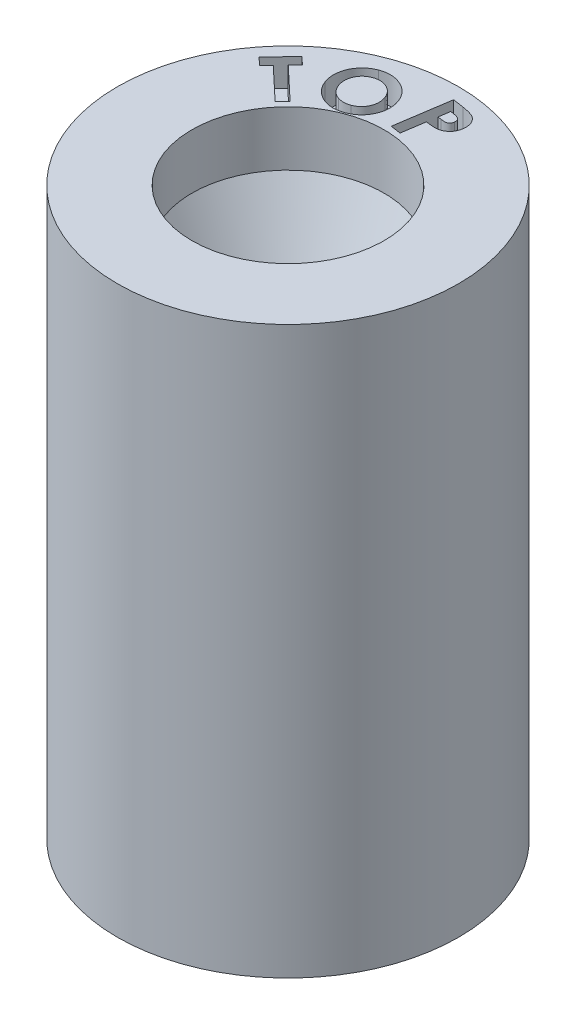
SolidWorks part; units mm, degrees
ref_plane "Front Plane" through (0, 0, 0) normal (0, 0, 1) x (1, 0, 0)
ref_plane "Top Plane" through (0, 0, 0) normal (0, 1, 0) x (1, 0, 0)
ref_plane "Right Plane" through (0, 0, 0) normal (1, 0, 0) x (0, 0, -1)
sketch "Sketch1" plane through (0, 0, 0) normal (0, 0, 1) x (1, 0, 0)
  line L0 (-6.2126, 20.6113) -> (-6.2126, 0)
  line L1 (-6.2126, 0) -> (-3.6286, 0)
  line L2 (-3.6286, 0) -> (-3.6286, 1)
  line L3 (-3.6286, 1) -> (-5.2126, 1) construction
  line L4 (-5.2126, 1) -> (-5.2126, 5) construction
  line L5 (-5.2126, 5) -> (-2.2594, 2.0469) construction
  line L6 (-2.2594, 2.0469) -> (-5.2126, 8.3161) construction
  line L7 (-5.2126, 8.3161) -> (-5.2126, 10.3161) construction
  line L8 (-5.2126, 10.3161) -> (-2.3594, 7.4629) construction
  line L9 (-2.3594, 7.4629) -> (-5.2126, 13.5198) construction
  line L10 (-5.2126, 13.5198) -> (-5.2126, 15.5198) construction
  line L11 (-5.2126, 15.5198) -> (-2.4594, 12.7667) construction
  line L12 (-5.2126, 10.3161) -> (-5.2126, 13.5198) construction
  line L13 (-5.2126, 5) -> (-5.2126, 8.3161) construction
  line L14 (-2.4594, 12.7667) -> (-5.2126, 18.6113) construction
  line L15 (-5.2126, 18.6113) -> (-5.2126, 20.6113) construction
  line L16 (-3.15, 2.9374) -> (-3.15, 3.9374)
  line L17 (-3.25, 8.3535) -> (-3.25, 9.3535)
  line L18 (-3.35, 13.6573) -> (-3.35, 14.6573)
  line L19 (-3.35, 13.6573) -> (-5.2126, 15.5198) construction
  line L20 (-5.2126, 15.5198) -> (-5.2126, 18.6113) construction
  line L21 (-6.2126, 20.6113) -> (-5.2126, 20.6113)
  line L22 (-3.35, 14.6573) -> (-5.2126, 18.6113)
  line L23 (-5.2126, 10.3161) -> (-3.25, 8.3535) construction
  line L24 (-3.25, 9.3535) -> (-5.2126, 13.5198) construction
  line L25 (-5.2126, 8.3161) -> (-3.15, 3.9374) construction
  line L26 (-3.15, 2.9374) -> (-5.2126, 5) construction
  line L27 (-3.35, 13.6573) -> (-4.1901, 11.3492)
  line L28 (-4.1901, 11.3492) -> (-3.25, 9.3535)
  line L29 (-3.25, 8.3535) -> (-4.1131, 5.9821)
  line L30 (-4.1131, 5.9821) -> (-3.15, 3.9374)
  line L31 (-3.15, 2.9374) -> (-3.8552, 1)
  line L32 (-3.8552, 1) -> (-3.6286, 1)
  line L33 (-5.2126, 20.6113) -> (-3.5, 20.6113)
  line L34 (-3.5, 20.6113) -> (-3.5, 18.6113)
  line L35 (-3.5, 18.6113) -> (-5.2126, 18.6113)
  dimension "D3" = 1
  dimension "D2" = 45
  dimension "D4" = 45
  dimension "D5" = 45
  dimension "D1" = 1
  dimension "D9" = 3.6286
  dimension "D10" = 1
  dimension "D6" = 3.35
  dimension "D7" = 3.25
  dimension "D8" = 3.15
  dimension "D11" = 2
  dimension "D12" = 4
  dimension "D13" = 2
  dimension "D14" = 200
  dimension "D15" = 3.5
ref_axis "Axis1" through (0, 31.7469, 0) along (0, -1, 0)
revolve "Revolve1" add sketch "Sketch1" angle 360 about axis through (0, 31.7469, 0) along (0, -1, 0)
sketch "Sketch2" plane through (0, 20.6113, 0) normal (0, 1, 0) x (1, 0, 0)
  arc A0 (-3.1309, 2.1162) -> (3.3228, 1.7999) centre (0, 0) cw construction
  text T0 "TOP" font "Century Gothic" height 2
  point P5 (-4.2192, -0.47)
  point P6 (-3.9131, 1.1914)
  point P7 (-3.5415, 2.3938)
  point P8 (3.2136, 2.1903)
  point P9 (3.935, 2.1315)
extrude "Cut-Extrude1" cut sketch "Sketch2" against normal blind 1
equation "\"angle\"=45"
equation "\"D2@Sketch1\"=\"angle\""
equation "\"D4@Sketch1\"=\"angle\""
equation "\"D5@Sketch1\"=\"angle\""
